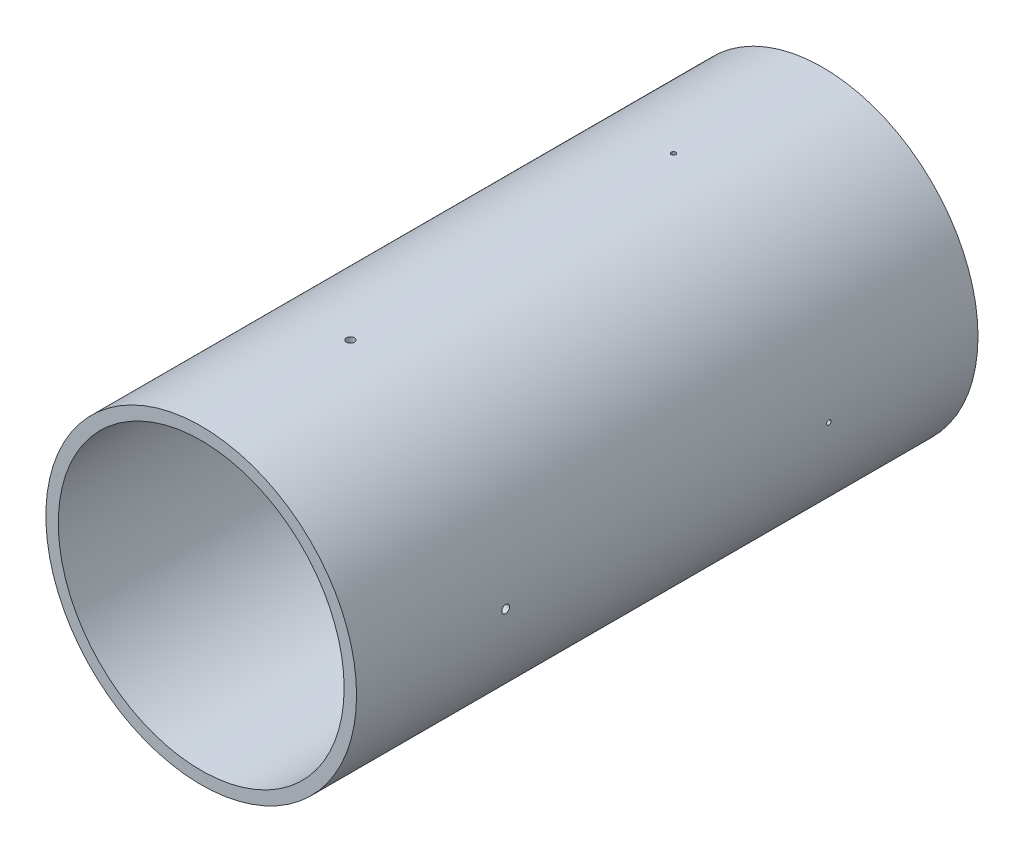
SolidWorks part; units mm, degrees
ref_plane "Front Plane" through (0, 0, 0) normal (0, 0, 1) x (1, 0, 0)
ref_plane "Top Plane" through (0, 0, 0) normal (0, 1, 0) x (1, 0, 0)
ref_plane "Right Plane" through (0, 0, 0) normal (1, 0, 0) x (0, 0, -1)
sketch "Sketch1" plane through (0, 0, 0) normal (0, 0, 1) x (1, 0, 0)
  circle A0 centre (0, 0) radius 79.375
  circle A1 centre (0, 0) radius 73.025
  dimension "D1" = 158.75
  dimension "D2" = 6.35
extrude "Boss-Extrude1" add sketch "Sketch1" along normal blind 317.5
ref_plane "Plane1" through (0, 79.375, 0) normal (0, 1, 0) x (1, 0, 0)
sketch "Sketch2" plane through (0, 79.375, 0) normal (0, 1, 0) x (1, 0, 0)
  line L0 (79.375, 0) -> (-79.375, 0) construction
  point P0 (0, -76.2)
  dimension "D1" = 76.2
hole_wizard "#4-40 Tapped Hole1" positions "Sketch5" profile "Sketch6" tap size "#4-40" standard "ANSI Inch" end condition up to next
sketch "Sketch5" plane through (0, 79.375, 0) normal (0, 1, 0) x (1, 0, 0)
  point P0 (0, -76.2)
sketch "Sketch6" plane through (0, 79.375, 76.2) normal (1, 0, 0) x (0, 0, 1)
  line L0 (0, 0) -> (0, 6.35)
  line L1 (0, 6.35) -> (1.1303, 6.35)
  line L2 (1.1303, 6.35) -> (1.1303, 0)
  line L5 (1.1303, 0) -> (0, 0)
  line L11 (0, -6.35) -> (0, 107.95) construction
  dimension "Thru Tap Drill Dia." = 2.2606
  dimension "Thru Tap Drill Depth" = 6.35
cosmetic thread "Hole Thread1"
sketch "Sketch7" plane through (0, 79.375, 0) normal (0, 1, 0) x (1, 0, 0)
  line L0 (-79.375, -317.5) -> (79.375, -317.5) construction
  point P0 (0, -241.3)
  dimension "D1" = 76.2
hole_wizard "#10-32 Tapped Hole1" positions "Sketch8" profile "Sketch9" tap size "#10-32" standard "ANSI Inch" end condition up to next
sketch "Sketch8" plane through (0, 79.375, 0) normal (0, 1, 0) x (1, 0, 0)
  point P0 (0, -241.3)
sketch "Sketch9" plane through (0, 79.375, 241.3) normal (1, 0, 0) x (0, 0, 1)
  line L0 (0, 0) -> (0, 6.35)
  line L1 (0, 6.35) -> (2.0193, 6.35)
  line L2 (2.0193, 6.35) -> (2.0193, 0)
  line L5 (2.0193, 0) -> (0, 0)
  line L11 (0, -6.35) -> (0, 107.95) construction
  dimension "Thru Tap Drill Dia." = 4.0386
  dimension "Thru Tap Drill Depth" = 6.35
cosmetic thread "Hole Thread2"
pattern_circular "CirPattern1" count 4 over 360 about axis through (0, 0, 317.5) along (0, 0, 1) of "#4-40 Tapped Hole1", "#10-32 Tapped Hole1"
cosmetic thread "Hole Thread3"
cosmetic thread "Hole Thread4"
cosmetic thread "Hole Thread5"
cosmetic thread "Hole Thread6"
cosmetic thread "Hole Thread7"
cosmetic thread "Hole Thread8"
